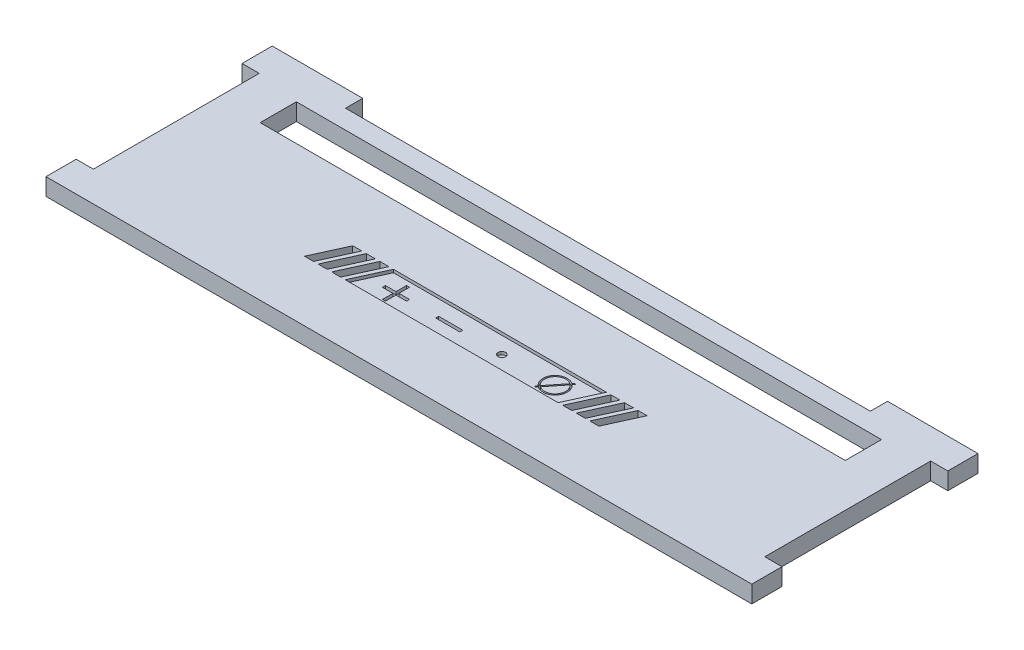
SolidWorks part; units mm, degrees
ref_plane "Front Plane" through (0, 0, 0) normal (0, 0, 1) x (1, 0, 0)
ref_plane "Top Plane" through (0, 0, 0) normal (0, 1, 0) x (1, 0, 0)
ref_plane "Right Plane" through (0, 0, 0) normal (1, 0, 0) x (0, 0, -1)
sketch "Sketch1" plane through (0, 0, 0) normal (0, 1, 0) x (1, 0, 0)
  line L1 (0, 0) -> (234, 0)
  line L2 (0, 0) -> (0, 75)
  line L3 (0, 75) -> (234, 75)
  line L4 (234, 0) -> (234, 75)
  dimension "D1" = 234
  dimension "D2" = 75
extrude "Boss-Extrude1" add sketch "Sketch1" along normal blind 5.7
sketch "Sketch2" plane through (0, 5.7, 0) normal (0, 1, 0) x (1, 0, 0)
  line L0 (0, 75) -> (0, 0) construction
  line L1 (0, 65) -> (5.7, 65)
  line L2 (0, 65) -> (0, 10)
  line L3 (0, 10) -> (5.7, 10)
  line L4 (5.7, 65) -> (5.7, 10)
  line L5 (0, 0) -> (234, 0) construction
  line L6 (234, 75) -> (0, 75) construction
  line L7 (234, 0) -> (234, 75) construction
  line L8 (234, 65) -> (228.3, 65)
  line L9 (234, 65) -> (234, 10)
  line L10 (234, 10) -> (228.3, 10)
  line L11 (228.3, 65) -> (228.3, 10)
  dimension "D1" = 10
  dimension "D2" = 10
  dimension "D3" = 5.7
  dimension "D4" = 10
  dimension "D5" = 10
  dimension "D6" = 5.7
extrude "Cut-Extrude1" cut sketch "Sketch2" against normal blind 5.7
sketch "Sketch3" plane through (0, 5.7, 0) normal (0, 1, 0) x (1, 0, 0)
  line L1 (214, 51) -> (20, 51)
  line L2 (214, 51) -> (214, 63)
  line L3 (214, 63) -> (20, 63)
  line L4 (20, 51) -> (20, 63)
  line L5 (234, 65) -> (234, 75) construction
  line L6 (0, 75) -> (0, 65) construction
  line L7 (234, 75) -> (0, 75) construction
  dimension "D1" = 20
  dimension "D2" = 20
  dimension "D3" = 12
  dimension "D4" = 12
extrude "Cut-Extrude2" cut sketch "Sketch3" against normal blind 5.7
sketch "Sketch4" plane through (0, 5.7, 0) normal (0, 1, 0) x (1, 0, 0)
  line L7 (234, 75) -> (0, 75) construction
  line L8 (30, 75) -> (204, 75)
  line L9 (30, 75) -> (30, 69.3)
  line L10 (30, 69.3) -> (204, 69.3)
  line L11 (204, 75) -> (204, 69.3)
  line L12 (0, 75) -> (0, 65) construction
  line L13 (234, 65) -> (234, 75) construction
  dimension "D4" = 30
  dimension "D5" = 30
  dimension "D6" = 5.7
extrude "Cut-Extrude3" cut sketch "Sketch4" against normal blind 5.7
sketch "Sketch5" plane through (0, 5.7, 0) normal (0, 1, 0) x (1, 0, 0)
  line L0 (5.7, 10) -> (5.7, 65) construction
  line L1 (65.7, 31) -> (168.3, 31)
  line L2 (65.7, 31) -> (65.7, 20)
  line L3 (65.7, 20) -> (168.3, 20)
  line L4 (168.3, 31) -> (168.3, 20)
  line L5 (228.3, 65) -> (228.3, 10) construction
  line L6 (20, 51) -> (214, 51) construction
  line L7 (0, 0) -> (234, 0) construction
  line L8 (168.3, 31) -> (163.3, 20)
  line L9 (65.7, 20) -> (70.7, 31)
  line L10 (68.7, 20) -> (73.7, 31)
  line L11 (70.2, 20) -> (75.2, 31)
  line L12 (73.2, 20) -> (78.2, 31)
  line L13 (160.3, 20) -> (165.3, 31)
  line L14 (158.8, 20) -> (163.8, 31)
  line L15 (155.8, 20) -> (160.8, 31)
  line L16 (74.7, 20) -> (79.7, 31)
  line L17 (154.3, 20) -> (159.3, 31)
  line L18 (79.2, 20) -> (84.2, 31)
  line L19 (77.7, 20) -> (82.7, 31)
  line L20 (151.3, 20) -> (156.3, 31)
  line L21 (149.8, 20) -> (154.8, 31)
  line L22 (96.85, 20) -> (101.85, 31)
  line L23 (114.5, 20) -> (119.5, 31)
  line L24 (132.15, 20) -> (137.15, 31)
  line L25 (145.8, 28.6225) -> (140.8, 22.3775) construction
  line L26 (146.4639, 29.0517) -> (140.5264, 21.6358)
  line L27 (146.0736, 29.3642) -> (140.1361, 21.9483)
  line L28 (140.1361, 21.9483) -> (140.5264, 21.6358)
  line L29 (146.4639, 29.0517) -> (146.0736, 29.3642)
  line L30 (108.175, 20) -> (108.175, 25.5) construction
  line L31 (117, 25.5) -> (99.35, 25.5) construction
  line L32 (108.175, 25.5) -> (108.175, 31) construction
  line L33 (99.35, 25.5) -> (81.7, 25.5) construction
  line L34 (90.525, 25.5) -> (90.525, 20) construction
  line L35 (90.525, 25.5) -> (90.525, 31) construction
  line L36 (90.025, 25) -> (86.525, 25)
  line L37 (112.175, 25) -> (104.175, 25)
  line L38 (112.175, 25) -> (112.175, 26)
  line L39 (112.175, 26) -> (104.175, 26)
  line L40 (104.175, 25) -> (104.175, 26)
  line L41 (91.025, 21.5) -> (90.025, 21.5)
  line L42 (91.025, 21.5) -> (91.025, 25)
  line L43 (91.025, 29.5) -> (90.025, 29.5)
  line L44 (90.025, 21.5) -> (90.025, 25)
  line L45 (94.525, 25) -> (91.025, 25)
  line L46 (94.525, 25) -> (94.525, 26)
  line L47 (94.525, 26) -> (91.025, 26)
  line L48 (86.525, 25) -> (86.525, 26)
  line L49 (91.025, 26) -> (91.025, 29.5)
  line L50 (90.025, 26) -> (90.025, 29.5)
  line L51 (90.025, 26) -> (86.525, 26)
  circle A0 centre (143.3, 25.5) radius 4
  circle A1 centre (125.65, 25.5) radius 4
  circle A2 centre (143.3, 25.5) radius 3.5
  circle A3 centre (125.65, 25.5) radius 1.25
  point P77 (90.525, 21.5)
  point P78 (0, 0)
  dimension "D21" = 8
  dimension "D22" = 8
  dimension "D27" = 0.5
  dimension "D33" = 2.5
  dimension "D1" = 60
  dimension "D2" = 60
  dimension "D3" = 20
  dimension "D4" = 20
  dimension "D5" = 5
  dimension "D6" = 3
  dimension "D7" = 1.5
  dimension "D8" = 3
  dimension "D9" = 3
  dimension "D10" = 1.5
  dimension "D11" = 3
  dimension "D12" = 1.5
  dimension "D13" = 1.5
  dimension "D14" = 3
  dimension "D15" = 1.5
  dimension "D16" = 3
  dimension "D17" = 1.5
  dimension "D18" = 17.65
  dimension "D19" = 17.65
  dimension "D20" = 17.65
  dimension "D23" = 6.5
  dimension "D24" = 5.5
  dimension "D25" = 6.5
  dimension "D26" = 5.5
  dimension "D28" = 2.5
  dimension "D29" = 0.25
  dimension "D30" = 0.25
  dimension "D31" = 0.75
  dimension "D32" = 0.75
  dimension "D34" = 0.5
  dimension "D35" = 0.5
  dimension "D36" = 4
  dimension "D37" = 4
  dimension "D38" = 4
  dimension "D39" = 4
  dimension "D40" = 4
  dimension "D41" = 4
  dimension "D42" = 0.5
  dimension "D43" = 0.5
  dimension "D44" = 0.5
  dimension "D45" = 0.5
extrude "Cut-Extrude4" cut sketch "Sketch5" against normal up to next contours L3 L10 L1 L9 | L3 L12 L1 L11 | L3 L19 L1 L16 | L20 L3 L17 L1 | L15 L3 L14 L1 | L13 L3 L8 L1 region at (69.7, 5.7, -25.5) region at (74.2, 5.7, -25.5) region at (78.7, 5.7, -25.5) region at (155.3, 5.7, -25.5) region at (159.8, 5.7, -25.5) region at (164.3, 5.7, -25.5)
extrude "Cut-Extrude5" cut sketch "Sketch5<6>" against normal blind 1 contours L3 L22 L1 L18 | L3 L23 L1 L22 | L3 L24 L1 L23 | L24 L3 L21 L1 | A2 L27 A0 | A0 L27 L28 L26 | A2 L26 A0 | A2 L27 A0 L26 | A2 L26 A0 L27 | A1 A3 | A3 | A0 L26 L29 L27 | A2 | L39 L40 L37 L38 | L50 L43 L49 L47 L46 L45 L42 L41 L44 L36 L48 L51 region at (93.025, 5.7, -30.7482) region at (110.675, 5.7, -30.7482) region at (128.325, 5.7, -30.7482) region at (145.975, 5.7, -30.7482) region at (146.0336, 5.7, -28.9142) region at (146.8721, 5.7, -27.0805) region at (145.642, 5.7, -28.4252) region at (145.3701, 5.7, -28.6357) region at (140.958, 5.7, -22.5748) region at (140.5664, 5.7, -22.0858) region at (121.7631, 5.7, -25.5) region at (125.65, 5.7, -25.5)
sketch "Sketch5<6>" plane through (0, 5.7, 0) normal (0, 1, 0) x (1, 0, 0) same geometry as "Sketch5"
extrude "Cut-Extrude7" cut sketch "Sketch5<9>" against normal blind 2 contours A2 L26 A0 | A0 L26 L29 L27 | A2 L26 A0 L27 | L26 A2 L27 | A0 L27 L28 L26 | A2 L27 A0 L26 | A2 L27 A0 | A3 | L50 L51 L48 L36 L44 L41 L42 L45 L46 L47 L49 L43 | L37 L40 L39 L38 region at (146.0336, 5.7, -28.9142) region at (146.8721, 5.7, -27.0805) region at (145.642, 5.7, -28.4252) region at (143.3, 5.7, -25.5) region at (145.3701, 5.7, -28.6357) region at (140.958, 5.7, -22.5748) region at (140.5664, 5.7, -22.0858) region at (90.525, 5.7, -25.5) region at (125.65, 5.7, -25.5)
sketch "Sketch5<9>" plane through (0, 5.7, 0) normal (0, 1, 0) x (1, 0, 0) same geometry as "Sketch5"
